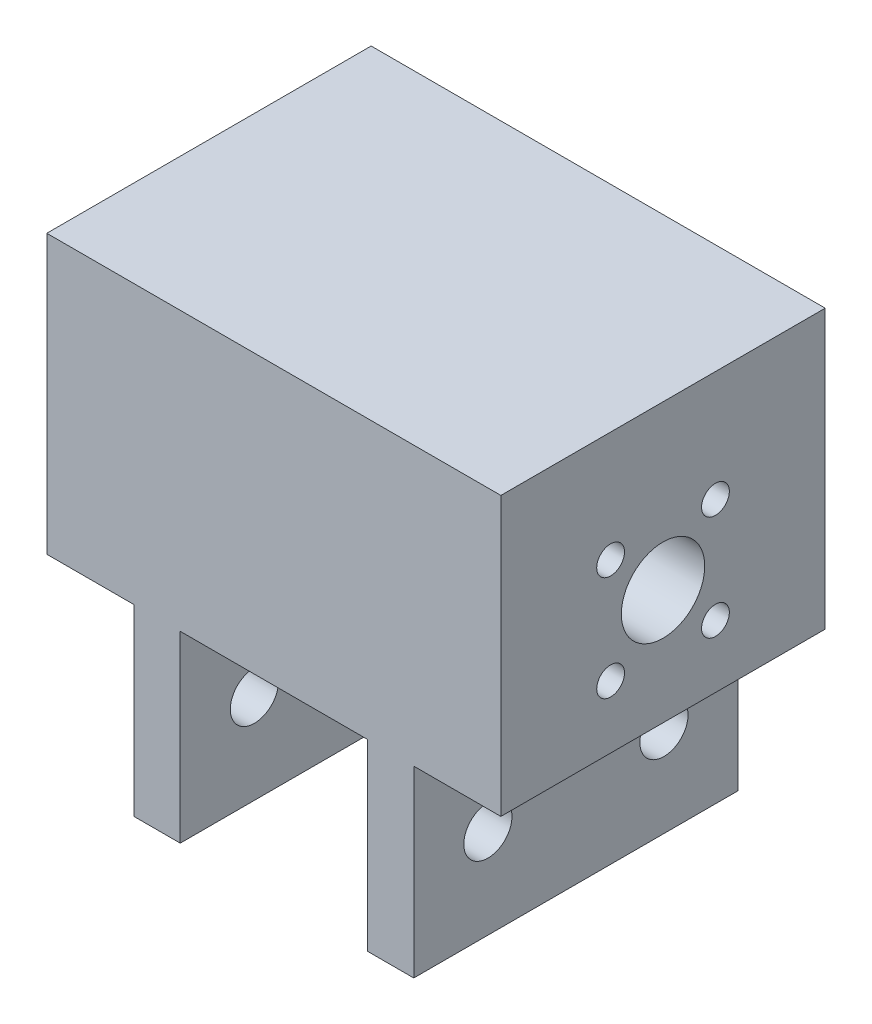
SolidWorks part; units mm, degrees
ref_plane "前视基准面" through (0, 0, 0) normal (0, 0, 1) x (1, 0, 0)
ref_plane "上视基准面" through (0, 0, 0) normal (0, 1, 0) x (1, 0, 0)
ref_plane "右视基准面" through (0, 0, 0) normal (1, 0, 0) x (0, 0, -1)
other "Configuration Table"
sketch "草图1" plane through (0, 0, 0) normal (0, 0, 1) x (1, 0, 0)
  line L0 (0, -39.6057) -> (0, 25.2485) construction
  line L9 (10.1, -34.8) -> (15.1, -34.8)
  line L10 (-24.5, -15) -> (-15.1, -15)
  line L11 (-24.5, -15) -> (-24.5, 15)
  line L12 (-24.5, 15) -> (24.5, 15)
  line L13 (24.5, -15) -> (24.5, 15)
  line L14 (-24.5, -15) -> (24.5, 15) construction
  line L15 (-24.5, 15) -> (24.5, -15) construction
  line L16 (-10.1, -15) -> (10.1, -15)
  line L17 (-15.1, -15) -> (-15.1, -34.8)
  line L18 (-15.1, -34.8) -> (-10.1, -34.8)
  line L19 (15.1, -15) -> (15.1, -34.8)
  line L21 (-10.1, -34.8) -> (-10.1, -15)
  line L22 (-10.1, -15) -> (10.1, -15)
  line L23 (10.1, -34.8) -> (10.1, -15)
  line L24 (-15.3981, -45.5587) -> (10.1, -15) construction
  line L25 (-10.1, -15) -> (18.7639, -49.5924) construction
  line L26 (-10.1, -15) -> (10.1, -15)
  line L27 (15.1, -15) -> (24.5, -15)
  point P2 (0, 0)
  point P12 (0, -27.1045)
  dimension "D1" = 49
  dimension "D2" = 30
  dimension "D3" = 19.8
  dimension "D4" = 5
  dimension "D5" = 20.2
extrude "凸台-拉伸1" add sketch "草图1" along normal blind 35 contours L19 L27 L13 L12 L11 L10 L17 L18 L21 L16 L23 L9 region at (0, -2.9558, 0)
hole_wizard "孔1" positions "草图4" profile "草图3" legacy end condition through all
sketch "草图4" plane through (-24.5, 0, 0) normal (-1, 0, 0) x (0, 0, 1)
  line L0 (17.5, 15) -> (17.5, -15) construction
  line L1 (35, 15) -> (0, 15) construction
  line L2 (35, -15) -> (0, -15) construction
  point P0 (17.5, -2.6)
  dimension "D1" = 12.4
sketch "草图3" plane through (-24.5, -2.6, 17.5) normal (0, 1, 0) x (0, 0, 1)
  line L0 (0, 0) -> (0, 49)
  line L1 (0, 49) -> (4.5, 49)
  line L2 (4.5, 49) -> (4.5, 0)
  line L3 (4.5, 0) -> (0, 0)
  line L4 (0, 110) -> (0, -10) construction
  dimension "直径" = 9
  dimension "深度" = 49
sketch "草图12" plane through (-24.5, 0, 0) normal (-1, 0, 0) x (0, 0, 1)
  line L1 (11.8431, -8.2569) -> (23.1569, -8.2569) construction
  line L2 (11.8431, -8.2569) -> (11.8431, 3.0569) construction
  line L3 (11.8431, 3.0569) -> (23.1569, 3.0569) construction
  line L4 (23.1569, -8.2569) -> (23.1569, 3.0569) construction
  line L5 (11.8431, -8.2569) -> (23.1569, 3.0569) construction
  line L6 (11.8431, 3.0569) -> (23.1569, -8.2569) construction
  circle A0 centre (17.5, -2.6) radius 8 construction
  circle A2 centre (11.8431, 3.0569) radius 1.5
  circle A3 centre (23.1569, 3.0569) radius 1.5
  circle A4 centre (23.1569, -8.2569) radius 1.5
  circle A5 centre (11.8431, -8.2569) radius 1.5
  dimension "D1" = 16
  dimension "D2" = 3
  dimension "D3" = 3
  dimension "D4" = 3
  dimension "D5" = 3
extrude "切除-拉伸1" cut sketch "草图12" against normal through all
sketch "草图15" plane through (-24.5, 0, 0) normal (-1, 0, 0) x (0, 0, 1)
  circle A0 centre (17.5, -2.6) radius 5.2
  dimension "D1" = 10.4
extrude "切除-拉伸4" cut sketch "草图15" against normal blind 16
sketch "草图14" plane through (-24.5, 0, 0) normal (-1, 0, 0) x (0, 0, 1)
  circle A0 centre (17.5, -2.6) radius 11.75
  dimension "D1" = 23.5
extrude "切除-拉伸3" cut sketch "草图14" against normal blind 4
hole_wizard "孔2" positions "草图16" profile "草图17" legacy
sketch "草图16" plane through (-15.1, 0, 0) normal (-1, 0, 0) x (0, 0, 1)
  line L0 (35, -15) -> (0, -15) construction
  line L1 (35, -15) -> (35, -34.8) construction
  line L2 (0, -15) -> (0, -34.8) construction
  point P0 (8, -25)
  point P2 (27, -25)
  dimension "D1" = 10
  dimension "D2" = 10
  dimension "D3" = 8
  dimension "D4" = 8
sketch "草图17" plane through (-15.1, -25, 8) normal (0, 1, 0) x (0, 0, 1)
  line L0 (0, 0) -> (0, 100)
  line L1 (0, 100) -> (2.6, 100)
  line L2 (2.6, 100) -> (2.6, 0)
  line L3 (2.6, 0) -> (0, 0)
  line L4 (0, 110) -> (0, -10) construction
  dimension "直径" = 5.2
  dimension "深度" = 100
